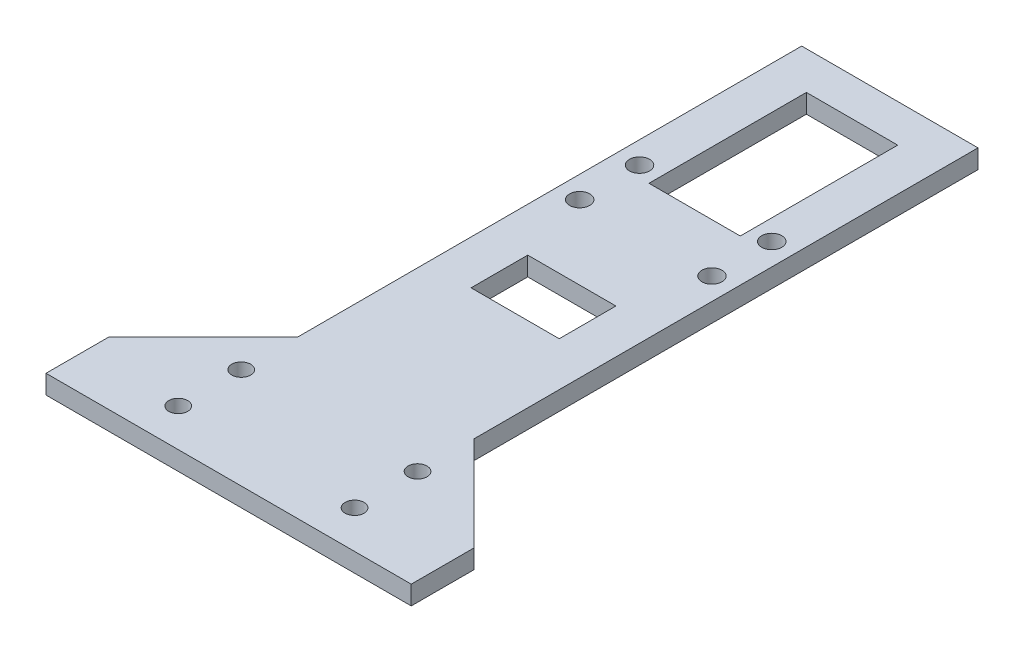
SolidWorks part; units mm, degrees
ref_plane "Front Plane" through (0, 0, 0) normal (0, 0, 1) x (1, 0, 0)
ref_plane "Top Plane" through (0, 0, 0) normal (0, 1, 0) x (1, 0, 0)
ref_plane "Right Plane" through (0, 0, 0) normal (1, 0, 0) x (0, 0, -1)
sketch "Sketch1" plane through (0, 0, 0) normal (0, 1, 0) x (1, 0, 0)
  line L0 (-14, -9) -> (-14, -91) construction
  line L2 (0, 0) -> (0, -80)
  line L4 (-28, 0) -> (-28, -80)
  line L5 (-14, -34) -> (-28, -34) construction
  line L11 (-21, -50.5) -> (-7, -50.5)
  line L12 (-21, -50.5) -> (-21, -59.5)
  line L13 (-21, -59.5) -> (-7, -59.5)
  line L14 (-7, -50.5) -> (-7, -59.5)
  line L17 (-28, 0) -> (0, 0)
  line L20 (-21.25, -6) -> (-6.75, -6)
  line L21 (-21.25, -6) -> (-21.25, -31)
  line L22 (-21.25, -31) -> (-6.75, -31)
  line L23 (-6.75, -6) -> (-6.75, -31)
  line L24 (-28, -80) -> (-43, -95)
  line L26 (0, -80) -> (15, -95)
  line L27 (-28, -80) -> (-28, -95) construction
  line L28 (0, -80) -> (0, -105.0292) construction
  line L29 (-43, -95) -> (-43, -105)
  line L30 (-43, -105) -> (15, -105)
  line L31 (15, -105) -> (15, -95)
  line L32 (-28, -89) -> (0, -89) construction
  line L33 (0, -89) -> (-28, -99) construction
  line L34 (-28, -99) -> (0, -99) construction
  line L35 (0, -99) -> (-28, -89) construction
  circle A0 centre (-24.5, -38.75) radius 1.6
  circle A1 centre (-3.5, -38.75) radius 1.6
  circle A2 centre (-3.5, -29.25) radius 1.6
  circle A3 centre (-24.5, -29.25) radius 1.6
  circle A4 centre (-28, -89) radius 1.5
  circle A5 centre (0, -89) radius 1.5
  circle A6 centre (-28, -99) radius 1.5
  circle A7 centre (0, -99) radius 1.5
  point P25 (-14, 0)
  dimension "D3" = 4.75
  dimension "D17" = 10
  dimension "D2" = 10.5
  dimension "D4" = 80
  dimension "D5" = 34
  dimension "D6" = 6.75
  dimension "D7" = 6.75
  dimension "D8" = 9
  dimension "D9" = 6
  dimension "D10" = 7
  dimension "D11" = 7
  dimension "D12" = 19.5
  dimension "D13" = 25
  dimension "D14" = 15
  dimension "D15" = 15
  dimension "D16" = 10
  dimension "D18" = 28
  dimension "D19" = 9
  dimension "D20" = 15
  dimension "D21" = 15
  dimension "D22" = 10
extrude "Boss-Extrude1" add sketch "Sketch1" along normal blind 3
